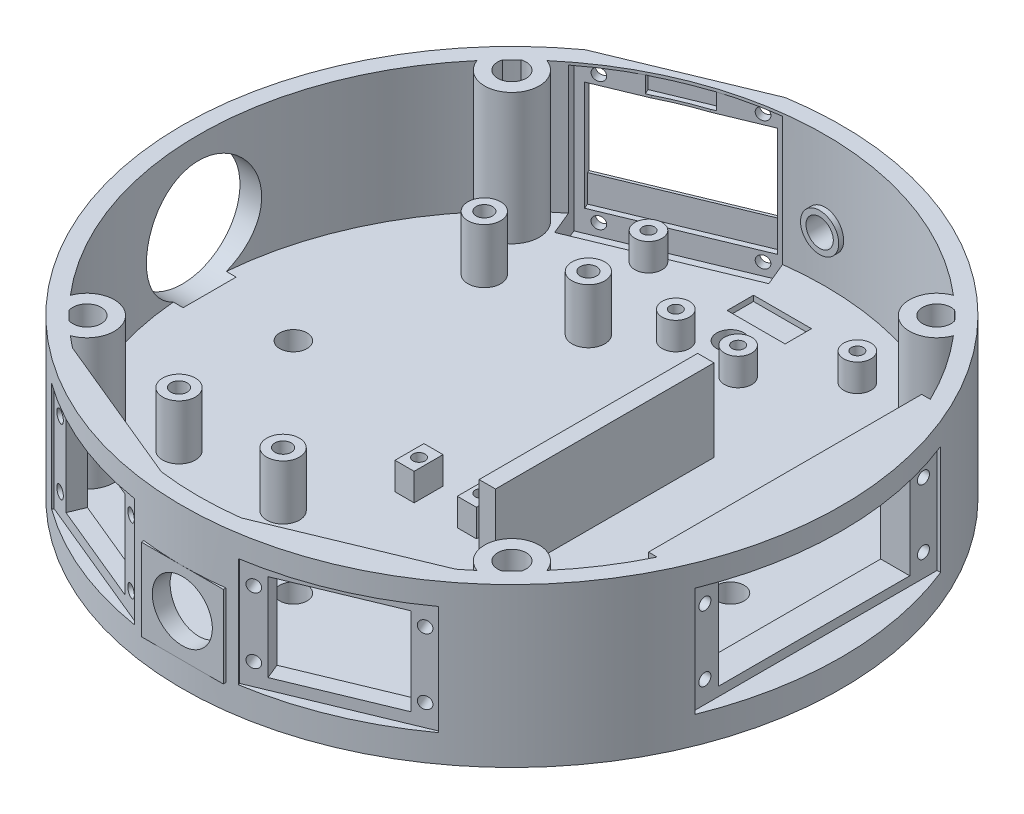
SolidWorks part; units mm, degrees
ref_plane "Front Plane" through (0, 0, 0) normal (0, 0, 1) x (1, 0, 0)
ref_plane "Top Plane" through (0, 0, 0) normal (0, 1, 0) x (1, 0, 0)
ref_plane "Right Plane" through (0, 0, 0) normal (1, 0, 0) x (0, 0, -1)
sketch "Sketch1" plane through (0, 0, 0) normal (0, 1, 0) x (1, 0, 0)
  circle A0 centre (0, 0) radius 60.325
  dimension "D1" = 120.65
extrude "Boss-Extrude1" add sketch "Sketch1" along normal blind 5
sketch "Sketch2" plane through (0, 5, 0) normal (0, 1, 0) x (1, 0, 0)
  line L9 (-15, -10) -> (15, -10)
  line L10 (-15, -10) -> (-15, 30)
  line L11 (-15, 30) -> (15, 30)
  line L12 (15, -10) -> (15, 30)
  line L13 (-15, -10) -> (15, 30) construction
  line L14 (-15, 30) -> (15, -10) construction
  point P0 (0.3114, 20.4789)
  point P5 (0, 10)
  dimension "D1" = 30
  dimension "D2" = 40
  dimension "D3" = 10
  dimension "D4" = 0
extrude "Boss-Extrude2" [suppressed] add sketch "Sketch2" along normal blind 20
sketch "Sketch3" plane through (0, 5, 0) normal (0, 1, 0) x (1, 0, 0)
  circle A0 centre (0, 0) radius 60.325
  circle A1 centre (0, 0) radius 57.325
  dimension "D1" = 114.65
  dimension "D2" = 3
extrude "Boss-Extrude3" add sketch "Sketch3" along normal blind 24
sketch "Sketch5" plane through (0, 5, 0) normal (0, 1, 0) x (1, 0, 0)
  line L0 (0, 0) -> (-38.8909, 38.8909)
  line L1 (0, 0) -> (38.8909, 38.8909)
  line L2 (0, 0) -> (-38.8909, -38.8909)
  line L3 (0, 0) -> (38.8909, -38.8909)
  circle A0 centre (-38.8909, 38.8909) radius 2.6
  circle A1 centre (-38.8909, 38.8909) radius 5
  circle A2 centre (38.8909, 38.8909) radius 2.6
  circle A3 centre (38.8909, 38.8909) radius 5
  circle A4 centre (-38.8909, -38.8909) radius 2.6
  circle A5 centre (-38.8909, -38.8909) radius 5
  circle A6 centre (38.8909, -38.8909) radius 2.6
  circle A7 centre (38.8909, -38.8909) radius 5
  circle A8 centre (0, 0) radius 60.325 construction
  circle M19 centre (0, 0) radius 57.325
  dimension "D1" = 5.2
  dimension "D2" = 10
  dimension "D3" = 5.2
  dimension "D4" = 10
  dimension "D5" = 10
  dimension "D6" = 5.2
  dimension "D7" = 5.2
  dimension "D8" = 10
  dimension "D9" = 55
  dimension "D10" = 55
  dimension "D11" = 55
  dimension "D12" = 55
ref_plane "Plane1" through (0, 0, 60.325) normal (0, 0, 1) x (1, 0, 0)
sketch "Sketch6" plane through (0, 0, 60.325) normal (0, 0, 1) x (1, 0, 0)
  line L1 (-7.5, 19.5) -> (7.5, 19.5)
  line L2 (-7.5, 19.5) -> (-7.5, 4.5)
  line L3 (-7.5, 4.5) -> (7.5, 4.5)
  line L4 (7.5, 19.5) -> (7.5, 4.5)
  line L5 (-7.5, 19.5) -> (7.5, 4.5) construction
  line L6 (-7.5, 4.5) -> (7.5, 19.5) construction
  point P0 (0, 12)
  dimension "D1" = 12
  dimension "D2" = 15
  dimension "D3" = 15
extrude "Boss-Extrude13" add sketch "Sketch6" against normal blind 2
sketch "Sketch7" plane through (0, 0, 60.325) normal (0, 0, 1) x (1, 0, 0)
  circle A0 centre (0, 12.3134) radius 5.5
  dimension "D1" = 11
extrude "Cut-Extrude1" cut sketch "Sketch7" against normal blind 5
sketch "Sketch8" [suppressed] plane through (0, 0, 10) normal (0, 0, 1) x (1, 0, 0)
  line L0 (-15, 5) -> (15, 5) construction
  line L1 (-12.0184, 27.5) -> (12.0184, 27.5)
  line L2 (-12.0184, 27.5) -> (-12.0184, 7.5)
  line L3 (-12.0184, 7.5) -> (12.0184, 7.5)
  line L4 (12.0184, 27.5) -> (12.0184, 7.5)
  line L5 (-12.0184, 27.5) -> (12.0184, 7.5) construction
  line L6 (-12.0184, 7.5) -> (12.0184, 27.5) construction
  point P0 (0, 17.5)
  dimension "D1" = 12.5
  dimension "D2" = 20
extrude "Cut-Extrude2" [suppressed] cut sketch "Sketch8" against normal blind 50
sketch "Sketch11" [suppressed] plane through (-15, 0, 0) normal (-1, 0, 0) x (0, 0, 1)
  line L0 (-30, 5) -> (10, 5) construction
  line L1 (-30, 25) -> (-30, 5) construction
  circle A0 centre (-15, 15) radius 2
  circle A1 centre (4, 15) radius 2
  dimension "D2" = 4
  dimension "D3" = 4
  dimension "D1" = 19
  dimension "D4" = 10
  dimension "D5" = 15
extrude "Cut-Extrude5" [suppressed] cut sketch "Sketch11" against normal blind 20
sketch "Sketch12" [suppressed] plane through (15, 0, 0) normal (1, 0, 0) x (0, 0, -1)
  line L0 (-10, 25) -> (-10, 5) construction
  line L1 (-10, 5) -> (30, 5) construction
  circle A0 centre (3, 15) radius 2
  circle A1 centre (26, 15) radius 2
  dimension "D3" = 4
  dimension "D4" = 4
  dimension "D1" = 23
  dimension "D2" = 13
  dimension "D5" = 10
extrude "Cut-Extrude6" [suppressed] cut sketch "Sketch12" against normal blind 20
ref_plane "Plane2" through (0, 0, -60.325) normal (0, 0, -1) x (-1, 0, 0)
ref_plane "Plane3" through (-60.325, 0, 0) normal (-1, 0, 0) x (0, 0, 1)
sketch "Sketch15" plane through (-60.325, 0, 0) normal (-1, 0, 0) x (0, 0, 1)
  circle A1 centre (0, 14.0795) radius 12.5
  dimension "D1" = 25
extrude "Boss-Extrude15" add sketch "Sketch15" against normal blind 3
sketch "Sketch16" plane through (-60.325, 0, 0) normal (-1, 0, 0) x (0, 0, 1)
  circle A0 centre (0, 14.3674) radius 10.55
  dimension "D1" = 21.1
extrude "Cut-Extrude9" cut sketch "Sketch16" against normal blind 5
sketch "Sketch17" plane through (0, 5, 0) normal (0, 1, 0) x (1, 0, 0)
  circle A0 centre (0, 40) radius 2.5
  circle A1 centre (40, 0) radius 2.5
  circle A2 centre (0, -40) radius 2.5
  circle A3 centre (-40, 0) radius 2.5
  dimension "D5" = 5
  dimension "D6" = 5
  dimension "D7" = 5
  dimension "D8" = 5
  dimension "D1" = 40
  dimension "D2" = 40
  dimension "D3" = 40
  dimension "D4" = 40
extrude "Cut-Extrude10" cut sketch "Sketch17" against normal blind 5
ref_plane "Plane4" through (60.325, 0, 0) normal (1, 0, 0) x (0, 0, -1)
sketch "Sketch20" plane through (0, 5, 0) normal (0, 1, 0) x (1, 0, 0)
  line L1 (-5.1053, 49.3333) -> (5.5119, 49.3333)
  line L2 (-5.1053, 49.3333) -> (-5.1053, 44.4903)
  line L3 (-5.1053, 44.4903) -> (5.5119, 44.4903)
  line L4 (5.5119, 49.3333) -> (5.5119, 44.4903)
  line L5 (-5.1053, 49.3333) -> (5.5119, 44.4903) construction
  line L6 (-5.1053, 44.4903) -> (5.5119, 49.3333) construction
  point P0 (0.2033, 46.9118)
extrude "Cut-Extrude13" cut sketch "Sketch20" against normal blind 1
ref_plane "Plane6" through (50, 0, 0) normal (1, 0, 0) x (0, 0, -1)
sketch "Sketch26" plane through (50, 0, 0) normal (1, 0, 0) x (0, 0, -1)
  line L1 (-25, 5) -> (25, 5)
  line L2 (-25, 5) -> (-25, 29)
  line L3 (-25, 29) -> (25, 29)
  line L4 (25, 5) -> (25, 29)
  line L5 (-25, 5) -> (25, 29) construction
  line L6 (-25, 29) -> (25, 5) construction
  point P0 (0, 17)
  dimension "D1" = 0
  dimension "D2" = 17
  dimension "D3" = 24
  dimension "D4" = 50
extrude "Boss-Extrude46" add sketch "Sketch26" along normal blind 10
sketch "Sketch27" plane through (60.325, 0, 0) normal (1, 0, 0) x (0, 0, -1)
  line L1 (-22.5, 5) -> (22.5, 5)
  line L2 (-22.5, 5) -> (-22.5, 25)
  line L3 (-22.5, 25) -> (22.5, 25)
  line L4 (22.5, 5) -> (22.5, 25)
  line L5 (-22.5, 5) -> (22.5, 25) construction
  line L6 (-22.5, 25) -> (22.5, 5) construction
  point P0 (0, 15)
  dimension "D1" = 45
  dimension "D2" = 20
  dimension "D3" = 0
  dimension "D4" = 15
extrude "Cut-Extrude15" cut sketch "Sketch27" against normal blind 5
sketch "Sketch28" plane through (60.325, 0, 0) normal (1, 0, 0) x (0, 0, -1)
  line L1 (-17.5, 23.3481) -> (17.5, 23.3481)
  line L2 (-17.5, 23.3481) -> (-17.5, 6.6519)
  line L3 (-17.5, 6.6519) -> (17.5, 6.6519)
  line L4 (17.5, 23.3481) -> (17.5, 6.6519)
  line L5 (-17.5, 23.3481) -> (17.5, 6.6519) construction
  line L6 (-17.5, 6.6519) -> (17.5, 23.3481) construction
  point P0 (0, 15)
  dimension "D1" = 35
  dimension "D2" = 15
  dimension "D3" = 0
sketch "Sketch29" plane through (55.325, 0, 0) normal (1, 0, 0) x (0, 0, -1)
  circle A0 centre (-20, 21) radius 1.1
  circle A1 centre (-20, 9) radius 1.1
  circle A2 centre (20, 21) radius 1.1
  circle A3 centre (20, 9.1519) radius 1.1
  dimension "D1" = 2.2
  dimension "D2" = 2.2
  dimension "D3" = 2.2
  dimension "D4" = 2.2
  dimension "D5" = 40
  dimension "D6" = 12
  dimension "D7" = 9
extrude "Cut-Extrude17" cut sketch "Sketch29" against normal blind 10
extrude "Cut-Extrude18" cut sketch "Sketch28" against normal blind 20
sketch "Sketch30" plane through (0, 29, 0) normal (0, 1, 0) x (1, 0, 0)
  line L0 (51.7831, 30.9453) -> (68.4097, 30.9453)
  line L1 (50.8846, -32.4016) -> (67.7321, -32.4016)
  arc A0 (50.8846, -32.4016) -> (51.7831, 30.9453) centre (0, 0) ccw
  arc A1 (67.7321, -32.4016) -> (68.4097, 30.9453) centre (0, 0) ccw
  dimension "D1" = 120.65
extrude "Boss-Extrude47" add sketch "Sketch5" along normal blind 24 contours L0 A1 A0 M19 | A1 L0 A0 M19 | A5 L2 A4 M19 | L2 A5 A4 M19 | A7 L3 A6 M19 | L3 A7 A6 M19 | L1 A3 A2 M19 | A3 L1 A2 M19 region at (-39.8437, 5, -35.9068) region at (-35.9068, 5, -39.8437) region at (35.9068, 5, -39.8437) region at (39.8437, 5, -35.9068) region at (-35.9068, 5, 39.8437) region at (-39.8437, 5, 35.9068) region at (39.8437, 5, 35.9068) region at (35.9068, 5, 39.8437)
extrude "Cut-Extrude19" cut sketch "Sketch30" against normal blind 30
sketch "Sketch31" plane through (0, 5, 0) normal (0, 1, 0) x (1, 0, 0)
  circle A0 centre (-33.05, 28) radius 3
  circle A1 centre (-14, 28) radius 3
  circle A2 centre (-14, -27.88) radius 3
  circle A3 centre (-33.05, -27.88) radius 3
  dimension "D9" = 6
  dimension "D10" = 6
  dimension "D11" = 6
  dimension "D12" = 6
  dimension "D2" = 55.88
  dimension "D3" = 14
  dimension "D4" = 14
  dimension "D5" = 19.05
  dimension "D6" = 28
  dimension "D7" = 55.88
  dimension "D8" = 0
  dimension "D13" = 19.05
extrude "Boss-Extrude48" add sketch "Sketch31" along normal blind 10
sketch "Sketch32" plane through (0, 15, 0) normal (0, 1, 0) x (1, 0, 0)
  circle A0 centre (-14, -27.88) radius 1.5
  circle A1 centre (-33.05, -27.88) radius 1.5
  circle A2 centre (-33.05, 28) radius 1.5
  circle A3 centre (-14, 28) radius 1.5
  dimension "D1" = 3
  dimension "D2" = 3
  dimension "D3" = 3
  dimension "D4" = 3
extrude "Cut-Extrude20" cut sketch "Sketch32" against normal blind 5
sketch "Sketch33" plane through (0, 5, 0) normal (0, 1, 0) x (1, 0, 0)
  line L9 (-6.75, -14.6471) -> (-3.25, -14.6471)
  line L10 (-6.75, -14.6471) -> (-6.75, -9.3529)
  line L11 (-6.75, -9.3529) -> (-3.25, -9.3529)
  line L12 (-3.25, -14.6471) -> (-3.25, -9.3529)
  line L13 (-6.75, -14.6471) -> (-3.25, -9.3529) construction
  line L14 (-6.75, -9.3529) -> (-3.25, -14.6471) construction
  line L15 (4.65, -14.6471) -> (8.15, -14.6471)
  line L16 (4.65, -14.6471) -> (4.65, -9.3529)
  line L17 (4.65, -9.3529) -> (8.15, -9.3529)
  line L18 (8.15, -14.6471) -> (8.15, -9.3529)
  line L19 (4.65, -14.6471) -> (8.15, -9.3529) construction
  line L20 (4.65, -9.3529) -> (8.15, -14.6471) construction
  circle A0 centre (-5, 35) radius 2.5
  circle A1 centre (6.4, 35.005) radius 2.5
  point P12 (-5, -12)
  point P17 (6.4, -12)
  dimension "D1" = 5
  dimension "D2" = 5
  dimension "D3" = 11.4
  dimension "D4" = 11.4
  dimension "D5" = 47
  dimension "D6" = 12
  dimension "D7" = 5
  dimension "D8" = 3.5
  dimension "D9" = 3.5
  dimension "D10" = 5
extrude "Boss-Extrude49" add sketch "Sketch33" along normal blind 5
sketch "Sketch34" plane through (0, 10, 0) normal (0, 1, 0) x (1, 0, 0)
  circle A1 centre (6.4, 35.005) radius 1.1
  circle A2 centre (6.4, -12) radius 1.1
  circle A3 centre (-5, -12) radius 1.1
  circle A4 centre (-5, 35) radius 1.1
  dimension "D1" = 2.2
  dimension "D2" = 2.2
  dimension "D3" = 2.2
  dimension "D4" = 2.2
  dimension "D5" = 12
  dimension "D6" = 12
extrude "Cut-Extrude21" cut sketch "Sketch34" against normal blind 5
sketch "Sketch35" plane through (0, 5, 0) normal (0, 1, 0) x (1, 0, 0)
  line L1 (14, 20) -> (17, 20)
  line L2 (14, 20) -> (14, -20)
  line L3 (14, -20) -> (17, -20)
  line L4 (17, 20) -> (17, -20)
  dimension "D1" = 17
  dimension "D2" = 3
  dimension "D3" = 40
  dimension "D4" = 20
extrude "Boss-Extrude50" add sketch "Sketch35" along normal blind 15
ref_axis "Axis1" through (0, 28.35, 0) along (0, -1, 0)
ref_plane "Plane8" through (-23.0854, 0, 55.733) normal (-0.3827, 0, 0.9239) x (0, -1, 0)
ref_plane "Plane9" through (0, 0, 0) normal (0.9239, 0, 0.3827) x (0, -1, 0)
ref_plane "Plane10" through (23.0854, 0, 55.733) normal (0.3827, 0, 0.9239) x (0, -1, 0)
ref_plane "Plane11" through (21.172, 0, 51.1136) normal (0.3827, 0, 0.9239) x (0, -1, 0)
sketch "Sketch39" plane through (21.172, 0, 51.1136) normal (0.3827, 0, 0.9239) x (0, -1, 0)
  line L1 (-29, 15.0144) -> (-5, 15.0144)
  line L2 (-29, 15.0144) -> (-29, -14.9856)
  line L3 (-29, -14.9856) -> (-5, -14.9856)
  line L4 (-5, 15.0144) -> (-5, -14.9856)
  dimension "D1" = 24
  dimension "D2" = 5
  dimension "D3" = 30
extrude "Boss-Extrude51" add sketch "Sketch39" along normal blind 2
sketch "Sketch37" plane through (23.0854, 0, 55.733) normal (0.3827, 0, 0.9239) x (0, -1, 0)
  line L1 (-25, 14) -> (-5, 14)
  line L2 (-25, 14) -> (-25, -14)
  line L3 (-25, -14) -> (-5, -14)
  line L4 (-5, 14) -> (-5, -14)
  dimension "D1" = 20
  dimension "D2" = 5
  dimension "D3" = 28
  dimension "D4" = 14
extrude "Cut-Extrude25" cut sketch "Sketch37" against normal blind 2
sketch "Sketch40" plane through (23.0854, 0, 55.733) normal (0.3827, 0, 0.9239) x (0, -1, 0)
  line L1 (-23, 10) -> (-7, 10)
  line L2 (-23, 10) -> (-23, -10)
  line L3 (-23, -10) -> (-7, -10)
  line L4 (-7, 10) -> (-7, -10)
  dimension "D1" = 16
  dimension "D2" = 7
  dimension "D3" = 10
  dimension "D4" = 20
extrude "Cut-Extrude26" cut sketch "Sketch40" against normal blind 12
sketch "Sketch41" plane through (23.0854, 0, 55.733) normal (0.3827, 0, 0.9239) x (0, -1, 0)
  circle A0 centre (-21, 12) radius 1.1
  circle A1 centre (-9, 12) radius 1.1
  circle A2 centre (-9, -12) radius 1.1
  circle A3 centre (-21, -12) radius 1.1
  dimension "D5" = 2.2
  dimension "D6" = 2.2
  dimension "D7" = 2.2
  dimension "D8" = 2.2
  dimension "D1" = 12
  dimension "D2" = 9
  dimension "D3" = 12
  dimension "D4" = 9
  dimension "D9" = 24
  dimension "D10" = 24
  dimension "D11" = 12
  dimension "D12" = 12
extrude "Cut-Extrude27" cut sketch "Sketch41" against normal blind 12
mirror "Mirror2" about plane through (0, 0, 0) normal (1, 0, 0) of "Boss-Extrude51", "Cut-Extrude25", "Cut-Extrude26", "Cut-Extrude27"
ref_plane "Plane12" through (-20.9232, 0, -50.5131) normal (0.3827, 0, 0.9239) x (0, -1, 0)
sketch "Sketch43" plane through (-20.9232, 0, -50.5131) normal (0.3827, 0, 0.9239) x (0, -1, 0)
  line L1 (-28.5, 15) -> (-1, 15)
  line L2 (-28.5, 15) -> (-28.5, -15)
  line L3 (-28.5, -15) -> (-1, -15)
  line L4 (-1, 15) -> (-1, -15)
  dimension "D1" = 30
  dimension "D2" = 27.5
  dimension "D3" = 1
  dimension "D4" = 15
extrude "Cut-Extrude28" cut sketch "Sketch43" against normal blind 2.5 and the other way blind 4
sketch "Sketch44" plane through (0, 5, 0) normal (0, 1, 0) x (1, 0, 0)
  circle A0 centre (-20, 45) radius 2.5
  circle A1 centre (45, -30) radius 2.5
  circle A2 centre (18.2295, 45) radius 2.5
  circle A3 centre (18.2295, -32.0272) radius 2.5
  point P11 (54.0648, -22.781)
  dimension "D3" = 5
  dimension "D4" = 5
  dimension "D5" = 5
  dimension "D8" = 5
  dimension "D1" = 20
  dimension "D2" = 45
  dimension "D6" = 45
  dimension "D7" = 30
extrude "Boss-Extrude52" add sketch "Sketch44" along normal blind 5
sketch "Sketch45" plane through (0, 10, 0) normal (0, 1, 0) x (1, 0, 0)
  circle A0 centre (-20, 45) radius 1.1
  circle A1 centre (18.2295, 45) radius 1.1
  circle A2 centre (18.2295, -32.0272) radius 1.1
  circle A3 centre (45, -30) radius 1.1
  dimension "D1" = 2.2
  dimension "D2" = 2.2
  dimension "D3" = 2.2
  dimension "D4" = 2.2
extrude "Cut-Extrude29" cut sketch "Sketch45" against normal blind 5
sketch "Sketch46" plane through (-21.8799, 0, -52.8228) normal (0.3827, 0, 0.9239) x (0.9239, 0, -0.3827)
  line L1 (-13.5, 25) -> (13.5, 25)
  line L2 (-13.5, 25) -> (-13.5, 10)
  line L3 (-13.5, 10) -> (13.5, 10)
  line L4 (13.5, 25) -> (13.5, 10)
  dimension "D1" = 27
  dimension "D2" = 15
  dimension "D3" = 10
  dimension "D4" = 13.5
extrude "Cut-Extrude30" cut sketch "Sketch46" against normal blind 5
sketch "Sketch47" plane through (-21.8799, 0, -52.8228) normal (0.3827, 0, 0.9239) x (0.9239, 0, -0.3827)
  circle A0 centre (11.5, 26.75) radius 1.1
  circle A1 centre (-11.5, 26.75) radius 1.1
  circle A2 centre (-11.5, 3.25) radius 1.1
  circle A3 centre (11.5, 3.25) radius 1.1
  dimension "D4" = 2.2
  dimension "D5" = 2.2
  dimension "D6" = 2.2
  dimension "D7" = 2.2
  dimension "D1" = 23
  dimension "D2" = 23.5
  dimension "D3" = 23
  dimension "D8" = 3.25
  dimension "D9" = 11.5
extrude "Cut-Extrude31" cut sketch "Sketch47" against normal blind 3
ref_plane "Plane13" through (-22.454, 0, -54.2086) normal (0.3827, 0, 0.9239) x (0, -1, 0)
sketch "Sketch48" plane through (-22.454, 0, -54.2086) normal (0.3827, 0, 0.9239) x (0, -1, 0)
  line L1 (-35, 15) -> (5, 15)
  line L2 (-35, 15) -> (-35, -15)
  line L3 (-35, -15) -> (5, -15)
  line L4 (5, 15) -> (5, -15)
  dimension "D1" = 30
  dimension "D2" = 15
  dimension "D3" = 5
  dimension "D4" = 40
extrude "Cut-Extrude32" cut sketch "Sketch48" against normal blind 5
sketch "Sketch49" plane through (-21.8799, 0, -52.8228) normal (0.3827, 0, 0.9239) x (0.9239, 0, -0.3827)
  line L1 (-5, 28.45) -> (5, 28.45)
  line L2 (-5, 28.45) -> (-5, 25.45)
  line L3 (-5, 25.45) -> (5, 25.45)
  line L4 (5, 28.45) -> (5, 25.45)
  line L5 (-13.5, 10) -> (13.5, 10)
  line L6 (-13.5, 10) -> (-13.5, 5)
  line L7 (-13.5, 5) -> (13.5, 5)
  line L8 (13.5, 10) -> (13.5, 5)
  dimension "D1" = 10
  dimension "D2" = 3
  dimension "D3" = 5
  dimension "D4" = 27
  dimension "D5" = 13.5
  dimension "D6" = 5
  dimension "D7" = 5
extrude "Cut-Extrude33" cut sketch "Sketch49" against normal blind 1
sketch "Sketch52" plane through (0, 0, -60.325) normal (0, 0, -1) x (-1, 0, 0)
  line L0 (0, 28.35) -> (0, -1.35) construction
  circle A0 centre (0, 14) radius 3.5
  point P4 (0, 16.5983)
  dimension "D1" = 7
  dimension "D2" = 14
extrude "Boss-Extrude54" add sketch "Sketch52" against normal blind 4
sketch "Sketch53" plane through (0, 0, -60.325) normal (0, 0, -1) x (-1, 0, 0)
  line L0 (0, 28.35) -> (0, -1.35) construction
  circle A0 centre (0, 14) radius 2.5
  dimension "D1" = 5
  dimension "D2" = 14
extrude "Cut-Extrude34" cut sketch "Sketch53" against normal blind 4
